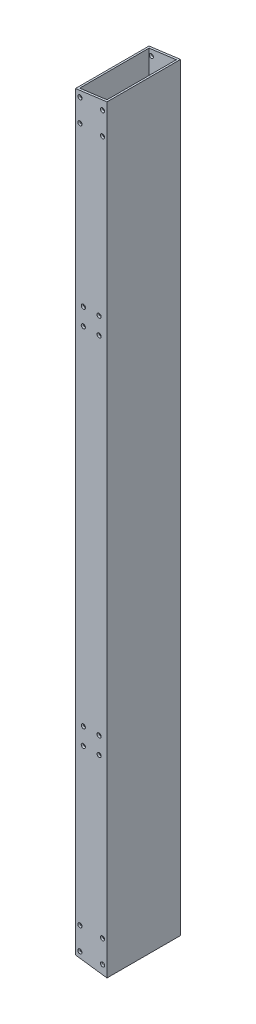
SolidWorks part; units mm, degrees
ref_plane "前视基准面" through (0, 0, 0) normal (0, 0, 1) x (1, 0, 0)
ref_plane "上视基准面" through (0, 0, 0) normal (0, 1, 0) x (1, 0, 0)
ref_plane "右视基准面" through (0, 0, 0) normal (1, 0, 0) x (0, 0, -1)
other "Configuration Table"
sketch "草图1" plane through (0, 0, 0) normal (0, 0, 1) x (1, 0, 0)
  line L1 (15, -375) -> (-15, -375)
  line L2 (15, -375) -> (15, 375)
  line L3 (15, 375) -> (-15, 375)
  line L4 (-15, -375) -> (-15, 375)
  line L5 (15, -375) -> (-15, 375) construction
  line L6 (15, 375) -> (-15, -375) construction
  circle A0 centre (-7.5, 194.9781) radius 2
  circle A1 centre (7.5, 194.9781) radius 2
  circle A2 centre (-7.5, 178.7736) radius 2
  circle A3 centre (7.5, 178.7736) radius 2
  circle A4 centre (-7.5, -150.8775) radius 2
  circle A5 centre (7.5, -150.8775) radius 2
  circle A6 centre (-7.5, -167.082) radius 2
  circle A7 centre (7.5, -167.082) radius 2
  point P0 (0, 0)
  dimension "D1" = 30
  dimension "D2" = 750
extrude "凸台-拉伸2" add sketch "草图1" along normal blind 70
sketch "草图2" plane through (0, -375, 0) normal (0, -1, 0) x (1, 0, 0)
  line L0 (-15, 70) -> (-15, 0) construction
  line L1 (-13, 68) -> (13, 68)
  line L2 (-13, 68) -> (-13, 2)
  line L3 (-13, 2) -> (13, 2)
  line L4 (13, 68) -> (13, 2)
  line L5 (-13, 68) -> (13, 2) construction
  line L6 (-13, 2) -> (13, 68) construction
  line L7 (-15, 70) -> (15, 70) construction
  line L8 (15, 70) -> (15, 0) construction
  line L9 (-15, 0) -> (15, 0) construction
  point P0 (0, 35)
  dimension "D1" = 2
  dimension "D2" = 2
  dimension "D3" = 2
  dimension "D4" = 2
extrude "切除-拉伸3" cut sketch "草图2" against normal through all contours L2 L1 L4 L3
sketch "草图3" plane through (0, 0, 70) normal (0, 0, 1) x (1, 0, 0)
  line L0 (15, 375) -> (-15, 371.0504)
  line L1 (-15, 375) -> (-15, -375) construction
  line L2 (15, -375) -> (15, 375) construction
  line L3 (15, -347.1) -> (-15, -343.1504)
  line L4 (-15, -343.1504) -> (-15, -376.6872)
  line L5 (-15, -376.6872) -> (15, -376.6872)
  line L6 (15, -376.6872) -> (15, -347.1)
  line L7 (-15, 371.0504) -> (-15, 377.0408)
  line L8 (-15, 377.0408) -> (15, 377.0408)
  line L9 (15, 377.0408) -> (15, 375)
  line M2 (-15, 375) -> (-15, -375)
  line M3 (-15, -375) -> (15, -375)
  line M4 (15, -375) -> (15, 375)
  dimension "D1" = 82.5
  dimension "D2" = 82.5
  dimension "D3" = 722.1
extrude "切除-拉伸4" cut sketch "草图3" against normal through all contours L3 M4 M2 M3 | L9 L0 L7 L8 region at (-0.3305, -360.0408, 70)
sketch "草图8" plane through (0, 0, 0) normal (0, 0, -1) x (-1, 0, 0)
  line L1 (15, -312.3178) -> (-15, -312.3178)
  line L2 (15, -312.3178) -> (15, -342.3178)
  line L3 (15, -342.3178) -> (-15, -342.3178)
  line L4 (-15, -312.3178) -> (-15, -342.3178)
  line L5 (15, 371.0504) -> (15, -343.1504) construction
  line L6 (15, 371.0504) -> (15, -343.1504)
  line L7 (-15, -347.1) -> (-15, 375) construction
  line L8 (-15, -347.1) -> (-15, 375)
  line L9 (15, -342.3178) -> (-15, -312.3178)
  line L10 (0, -342.3178) -> (0, -312.3178)
  line L11 (15, -327.3178) -> (-15, -327.3178)
  line L12 (-15, 13.95) -> (15, 13.95)
  circle A0 centre (10.7527, -338.0705) radius 2
  circle A1 centre (10.7527, -316.5651) radius 2
  circle A2 centre (-10.7527, -316.5651) radius 2
  circle A3 centre (-10.7527, -338.0705) radius 2
  circle A4 centre (-10.7527, 365.9705) radius 2
  circle A5 centre (-10.7527, 344.4651) radius 2
  circle A6 centre (10.7527, 344.4651) radius 2
  circle A7 centre (10.7527, 365.9705) radius 2
  dimension "D2" = 4
  dimension "D1" = 30
extrude "切除-拉伸6" cut sketch "草图8" against normal through all contours L9 A0 | L9 A0 | A3 | L9 A2 | L9 A2 | A1 | A4 | A5 | A6 | A7 region at (10.1525, -315.9649, 0) region at (11.3529, -317.1653, 0) region at (-11.3529, -337.4703, 0) region at (-10.1525, -338.6707, 0) region at (-10.7527, -316.5651, 0) region at (10.7527, -338.0705, 0) region at (10.7527, 365.9705, 0) region at (10.7527, 344.4651, 0) region at (-10.7527, 344.4651, 0) region at (-10.7527, 365.9705, 0)
